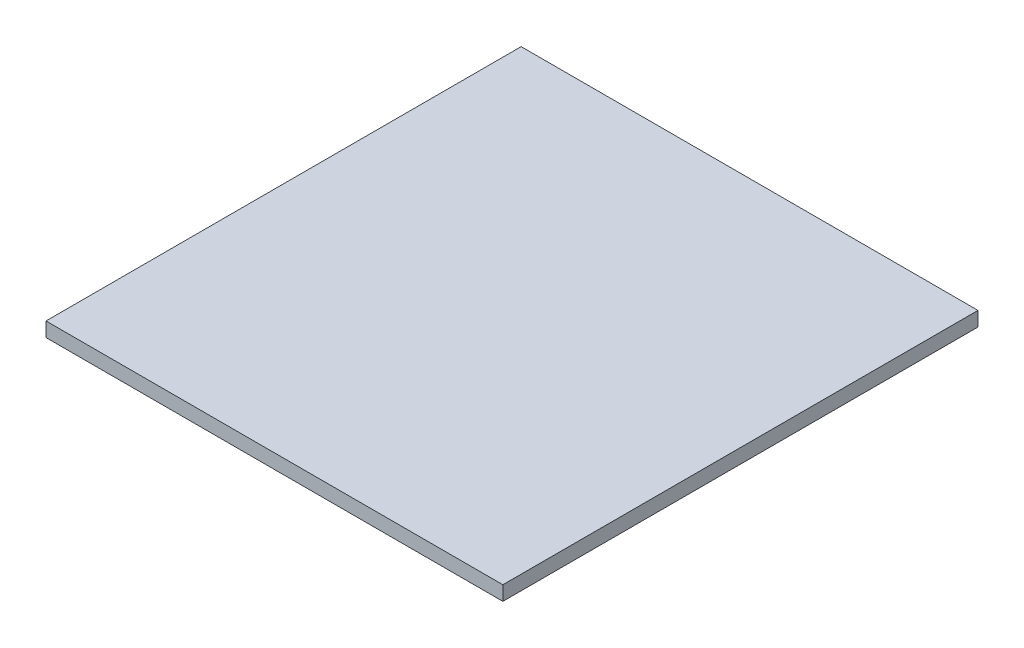
SolidWorks part; units mm, degrees
ref_plane "Front Plane" through (0, 0, 0) normal (0, 0, 1) x (1, 0, 0)
ref_plane "Top Plane" through (0, 0, 0) normal (0, 1, 0) x (1, 0, 0)
ref_plane "Right Plane" through (0, 0, 0) normal (1, 0, 0) x (0, 0, -1)
sketch "Sketch1" plane through (0, 0, 0) normal (0, 1, 0) x (1, 0, 0)
  line L1 (-44.2815, 20.698) -> (50.7185, 20.698)
  line L2 (-44.2815, 20.698) -> (-44.2815, -78.102)
  line L3 (-44.2815, -78.102) -> (50.7185, -78.102)
  line L4 (50.7185, 20.698) -> (50.7185, -78.102)
  dimension "D1" = 95
  dimension "D2" = 98.8
extrude "Boss-Extrude1" add sketch "Sketch1" along normal blind 3
equation "\"Fit\"= 1"
equation "\"cover width\"= 98.8"
equation "\"top 1 length\"= 95"
equation "\"thinner acrylic\"= 3"
equation "\"D1@Sketch1\"=\"top 1 length\""
equation "\"D2@Sketch1\"=\"cover width\""
equation "\"D1@Boss-Extrude1\"=\"thinner acrylic\""
